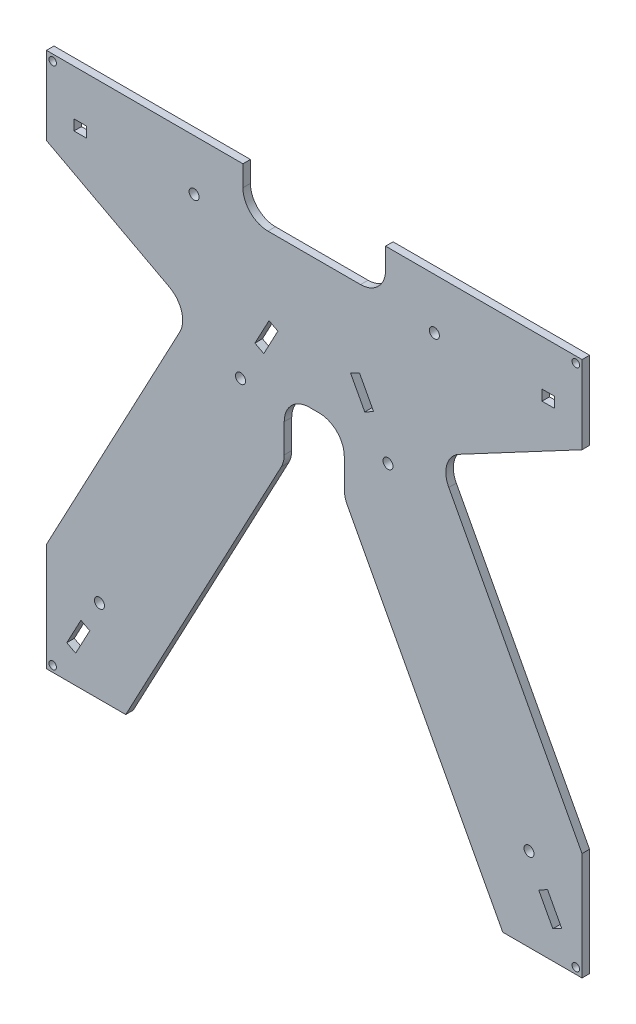
SolidWorks part; units mm, degrees
material "Oak"
ref_plane "Front Plane" through (0, 0, 0) normal (0, 0, 1) x (1, 0, 0)
ref_plane "Top Plane" through (0, 0, 0) normal (0, 1, 0) x (1, 0, 0)
ref_plane "Right Plane" through (0, 0, 0) normal (1, 0, 0) x (0, 0, -1)
sketch "Sketch1" plane through (0, 0, 0) normal (0, 0, 1) x (1, 0, 0)
  line L0 (15, 63.7) -> (104.5, -104.5) construction
  line L1 (0, 84.6) -> (0, 0) construction
  line L2 (89, 107) -> (107, 107)
  line L3 (-96, 86.7) -> (-91, 86.7) construction
  line L4 (-38, 88.7) -> (38, 88.7) construction
  line L5 (-38, 88.7) -> (-38, 84.7) construction
  line L6 (0, -91.5) -> (0, -107) construction
  line L7 (-107, -107) -> (107, -107)
  line L8 (-38, 84.7) -> (38, 84.7) construction
  line L9 (-107, 107) -> (-89, 107)
  line L10 (38, 88.7) -> (38, 84.7) construction
  line L11 (-107, -107) -> (107, 107) construction
  line L12 (-107, 107) -> (107, -107) construction
  line L13 (-96, 88.8) -> (-91, 88.8)
  line L14 (-96, 88.8) -> (-96, 84.6)
  line L15 (-96, 84.6) -> (-91, 84.6)
  line L16 (-91, 88.8) -> (-91, 84.6)
  line L17 (96, 88.8) -> (91, 88.8)
  line L18 (96, 88.8) -> (96, 84.6)
  line L19 (96, 84.6) -> (91, 84.6)
  line L20 (91, 88.8) -> (91, 84.6)
  line L21 (-38, 88.7) -> (38, 84.7) construction
  line L22 (-38, 84.7) -> (38, 88.7) construction
  line L23 (-15, 63.7) -> (15, 63.7) construction
  line L24 (-15, 63.7) -> (-15, 84.7) construction
  line L25 (-15, 84.7) -> (15, 84.7) construction
  line L26 (15, 63.7) -> (15, 84.7) construction
  line L27 (-15, 63.7) -> (15, 84.7) construction
  line L28 (-15, 84.7) -> (15, 63.7) construction
  line L29 (93.2262, -83.3127) -> (98.8631, -93.9064)
  line L30 (93.2262, -83.3127) -> (89.6949, -85.1917)
  line L31 (98.8631, -93.9064) -> (95.3319, -95.7853)
  line L32 (-107, 107) -> (-107, -107)
  line L33 (89.6949, -85.1917) -> (95.3319, -95.7853)
  line L34 (18.0672, 57.9357) -> (23.7041, 47.3421)
  line L35 (18.0672, 57.9357) -> (14.536, 56.0568)
  line L36 (23.7041, 47.3421) -> (20.1729, 45.4631)
  line L37 (-48, 86.7) -> (48, 86.7) construction
  line L38 (0, 84.6) -> (0, 88.8) construction
  line L39 (107, -107) -> (107, 107)
  line L40 (-89, 107) -> (89, 107)
  line L41 (14.536, 56.0568) -> (20.1729, 45.4631)
  line L42 (21.9385, 46.4026) -> (91.4605, -84.2522) construction
  line L43 (-93.2262, -83.3127) -> (-89.6949, -85.1917)
  line L44 (-89.6949, -85.1917) -> (-95.3319, -95.7853)
  line L45 (-98.8631, -93.9064) -> (-95.3319, -95.7853)
  line L46 (-93.2262, -83.3127) -> (-98.8631, -93.9064)
  line L47 (-18.0672, 57.9357) -> (-14.536, 56.0568)
  line L48 (-18.0672, 57.9357) -> (-23.7041, 47.3421)
  line L49 (-23.7041, 47.3421) -> (-20.1729, 45.4631)
  line L50 (-14.536, 56.0568) -> (-20.1729, 45.4631)
  circle A0 centre (-104.5, 104.5) radius 1.5
  circle A1 centre (104.5, 104.5) radius 1.5
  circle A2 centre (104.5, 0) radius 1.5
  circle A3 centre (-48, 86.7) radius 2
  circle A4 centre (0, 104.5) radius 1.5
  circle A5 centre (104.5, -104.5) radius 1.5
  circle A6 centre (0, 0) radius 2
  circle A7 centre (0, -104.5) radius 1.5
  circle A8 centre (-104.5, -104.5) radius 1.5
  circle A9 centre (-104.5, 0) radius 1.5
  circle A10 centre (48, 86.7) radius 2
  circle A11 centre (29.4544, 32.2778) radius 2
  circle A12 centre (85.8236, -73.6586) radius 2
  circle A13 centre (-85.8236, -73.6586) radius 2
  circle A14 centre (-29.4544, 32.2778) radius 2
  point P0 (0, 0)
  point P1 (0, 0)
  point P26 (0, 86.7)
  point P39 (0, 74.2)
  point P66 (0, 0)
  point P69 (0, 86.7)
  dimension "D4" = 3
  dimension "D16" = 4
  dimension "D23" = 48
  dimension "D9" = 4
  dimension "D8" = 17.8
  dimension "D2" = 182
  dimension "D3" = 214
  dimension "D5" = 209
  dimension "D6" = 4.2
  dimension "D7" = 5
  dimension "D10" = 18
  dimension "D11" = 21
  dimension "D12" = 30
  dimension "D13" = 4
  dimension "D14" = 12
  dimension "D15" = 4
  dimension "D17" = 12
  dimension "D18" = 148
  dimension "D19" = 24
  dimension "D20" = 120
extrude "Boss-Extrude1" add sketch "Sketch1" along normal blind 3
sketch "Sketch3" plane through (0, 0, 3) normal (0, 0, 1) x (1, 0, 0)
  line L0 (107, 107) -> (-107, 107) construction
  line L1 (-12, 12) -> (-75.3205, -107)
  line L2 (-107, -107) -> (107, -107) construction
  line L3 (-75.3205, -107) -> (75.3205, -107)
  line L4 (75.3205, -107) -> (12, 12)
  line L5 (-95.3319, -95.7853) -> (-89.6949, -85.1917) construction
  line L6 (89.6949, -85.1917) -> (95.3319, -95.7853) construction
  line L7 (-107, 75.7876) -> (-49.0566, 44.9557)
  line L8 (-107, 107) -> (-107, -107) construction
  line L9 (-49.0566, 44.9557) -> (-107, -63.9391)
  line L10 (-12, 12) -> (12, 12) construction
  line L11 (-12, 12) -> (-12, 36)
  line L12 (-12, 36) -> (12, 36)
  line L13 (12, 12) -> (12, 36)
  line L14 (-12, 12) -> (12, 36) construction
  line L15 (-12, 36) -> (12, 12) construction
  line L16 (-107, -63.9391) -> (-107, 75.7876)
  line L17 (0, 24) -> (0, 0) construction
  line L18 (107, -63.9391) -> (107, 75.7876)
  line L19 (49.0566, 44.9557) -> (107, -63.9391)
  line L20 (107, 75.7876) -> (49.0566, 44.9557)
  line L21 (-28.5, 88.7) -> (28.5, 88.7)
  line L22 (-28.5, 88.7) -> (-28.5, 107)
  line L23 (-28.5, 107) -> (28.5, 107)
  line L24 (28.5, 88.7) -> (28.5, 107)
  line L25 (-28.5, 88.7) -> (28.5, 107) construction
  line L26 (-28.5, 107) -> (28.5, 88.7) construction
  line L27 (0, 107) -> (0, 97.85) construction
  line L28 (-48, 86.7) -> (48, 86.7) construction
  point P10 (0, 24)
  point P24 (0, 104.5)
  dimension "D1" = 57
  dimension "D2" = 2
  dimension "D6" = 24
  dimension "D7" = 24
  dimension "D8" = 12
extrude "Cut-Extrude2" cut sketch "Sketch3" against normal through all
fillet "Fillet1" radius 10 8 edges at (49.0566, 44.9557, 1.5) (12, 12, 1.5) (-12, 12, 1.5) (-12, 36, 1.5) (12, 36, 1.5) (-49.0566, 44.9557, 1.5) (-28.5, 88.7, 1.5) (28.5, 88.7, 1.5)
equation "\"bed-plate-thickness\"=3"
equation "\"D1@Boss-Extrude1\"=\"bed-plate-thickness\""
equation "\"D6@Sketch1\" = \"y-cross-rib-thickness\" + 0.2"
equation "\"y-cross-rib-thickness\"=4"
equation "\"y-rib-thickness\"=6"
equation "\"x-plate-thickness\"=5"
equation "\"rod-diameter\"=12"
equation "\"t-nut-hole-diameter\"=3"
equation "\"D9@Sketch1\"=\"y-cross-rib-thickness\""
equation "\"D15@Sketch1\"=\"y-cross-rib-thickness\""
